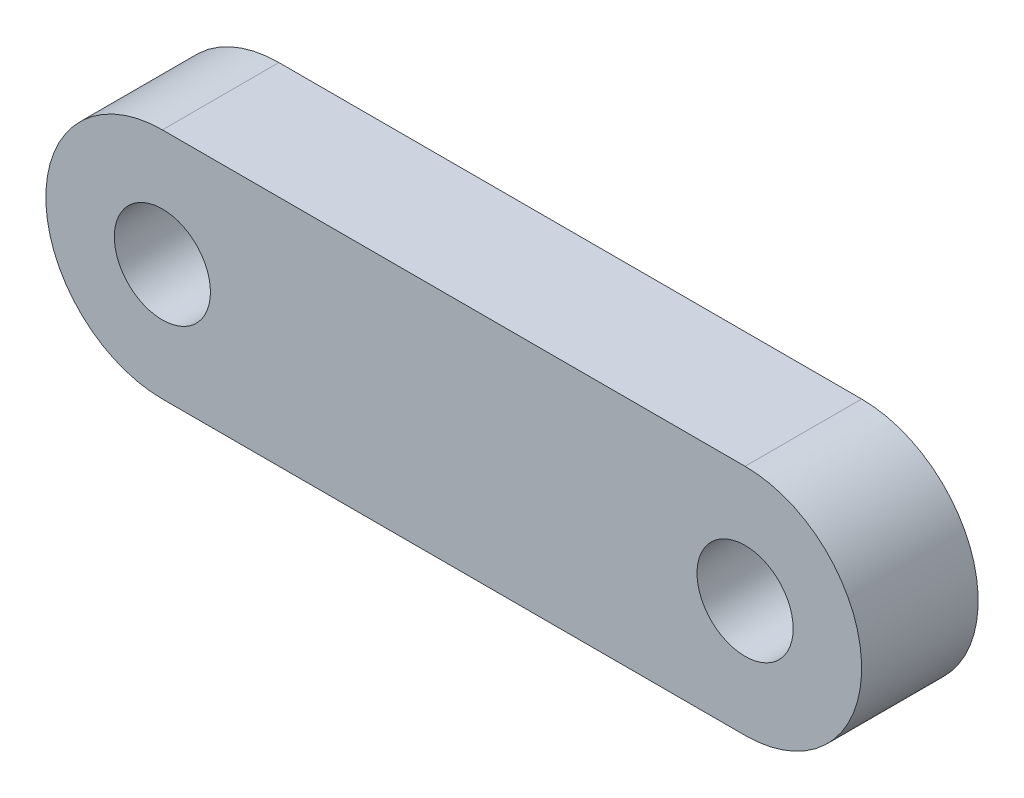
SolidWorks part; units mm, degrees
ref_plane "Front Plane" through (0, 0, 0) normal (0, 0, 1) x (1, 0, 0)
ref_plane "Top Plane" through (0, 0, 0) normal (0, 1, 0) x (1, 0, 0)
ref_plane "Right Plane" through (0, 0, 0) normal (1, 0, 0) x (0, 0, -1)
sketch "Sketch1" plane through (0, 0, 0) normal (0, 0, 1) x (1, 0, 0)
  line L0 (-20, 4) -> (0, 4)
  line L1 (-20, -4) -> (0, -4)
  arc A0 (0, -4) -> (0, 4) centre (0, 0) ccw
  circle A1 centre (0, 0) radius 1.65
  circle A2 centre (-20, 0) radius 1.65
  arc A3 (-20, 4) -> (-20, -4) centre (-20, 0) ccw
  dimension "D1" = 8
  dimension "D2" = 3.3
  dimension "D3" = 20
extrude "Boss-Extrude1" add sketch "Sketch1" along normal blind 4
